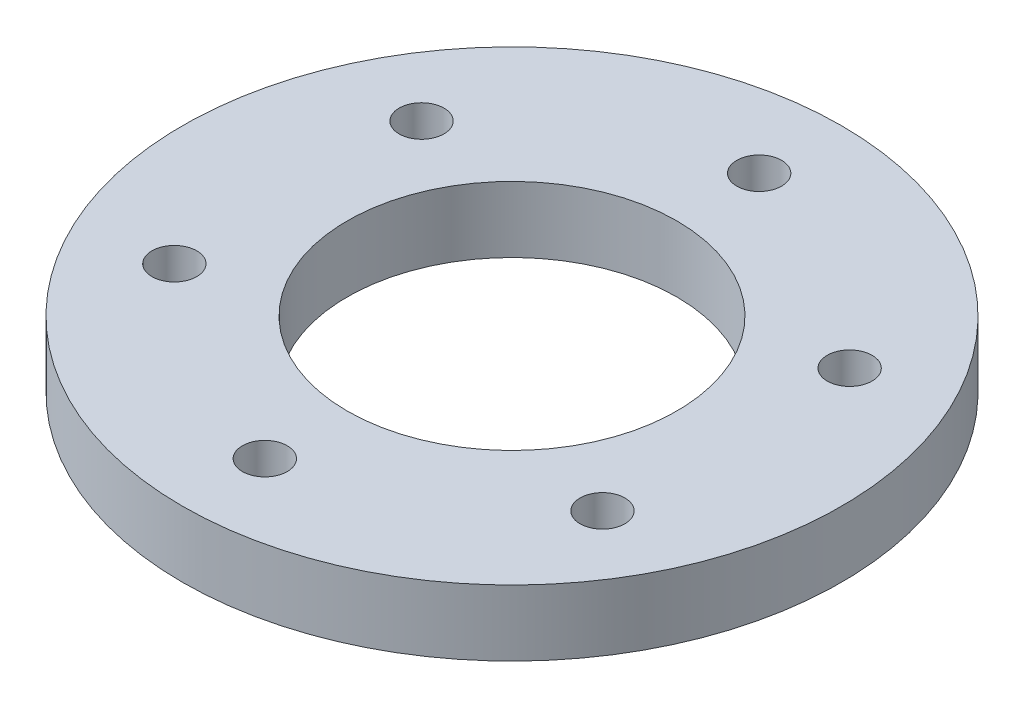
SolidWorks part; units mm, degrees
material "6061-T6 (SS)"
ref_plane "Front Plane" through (0, 0, 0) normal (0, 0, 1) x (1, 0, 0)
ref_plane "Top Plane" through (0, 0, 0) normal (0, 1, 0) x (1, 0, 0)
ref_plane "Right Plane" through (0, 0, 0) normal (1, 0, 0) x (0, 0, -1)
sketch "Sketch1" plane through (0, 0, 0) normal (0, 1, 0) x (1, 0, 0)
  line L0 (0, 23.8125) -> (0, 0) construction
  line L1 (0, 0) -> (20.6222, 11.9062) construction
  circle A5 centre (0, 0) radius 31.75
  circle A6 centre (0, 0) radius 15.875
  circle A11 centre (0, 23.8125) radius 2.159
  circle A13 centre (0, 0) radius 23.8125 construction
  circle A15 centre (20.6222, -11.9063) radius 2.159
  circle A16 centre (0, -23.8125) radius 2.159
  circle A17 centre (-20.6222, -11.9063) radius 2.159
  circle A18 centre (-20.6222, 11.9063) radius 2.159
  circle A19 centre (20.6222, 11.9063) radius 2.159 [skipped]
  circle A20 centre (20.6222, 11.9062) radius 2.159
  point P20 (0, 0)
  dimension "D3" = 60
  dimension "D4" = 6
  dimension "D5" = 47.625
  dimension "D6" = 31.75
  dimension "D1" = 63.5
  dimension "D2" = 4.318
extrude "Boss-Extrude2" add sketch "Sketch1" along normal blind 6.35 contours A5 A16 A11 A15 A6 region at (-30.852, 0, 0)
